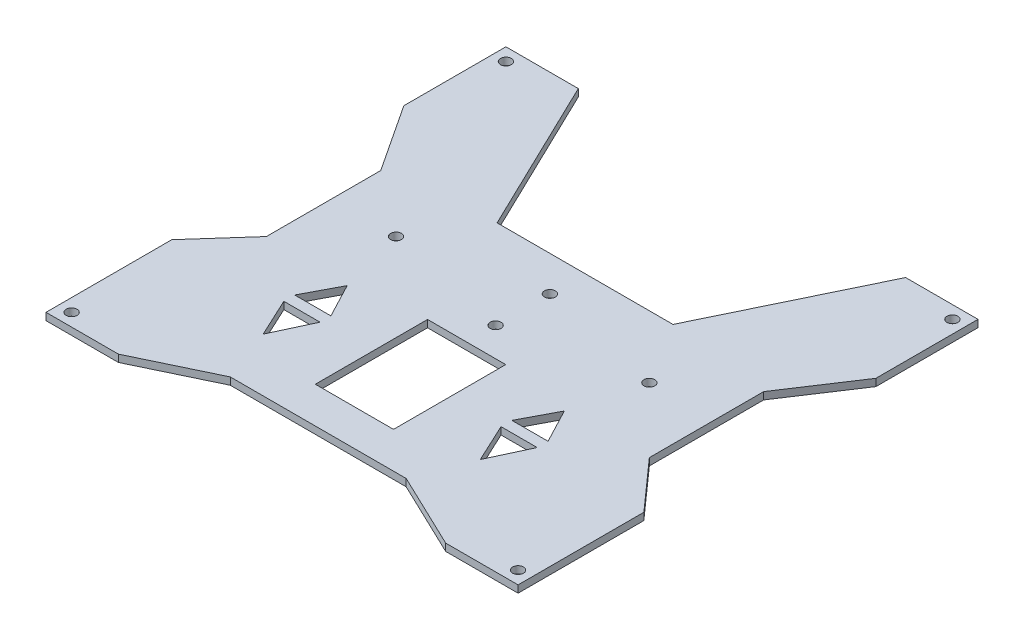
SolidWorks part; units mm, degrees
ref_plane "Front Plane" through (0, 0, 0) normal (0, 0, 1) x (1, 0, 0)
ref_plane "Top Plane" through (0, 0, 0) normal (0, 1, 0) x (1, 0, 0)
ref_plane "Right Plane" through (0, 0, 0) normal (1, 0, 0) x (0, 0, -1)
sketch "Sketch1" plane through (0, 0, 0) normal (0, 1, 0) x (1, 0, 0)
  line L0 (0, 0) -> (123.36, 0) construction
  line L1 (123.36, 0) -> (123.36, -120) construction
  line L2 (0, 0) -> (0, -120) construction
  line L3 (0, 0) -> (-3.5355, 3.5355) construction
  line L4 (123.36, -120) -> (126.8955, -123.5355) construction
  line L6 (-3.5355, 3.5355) -> (126.8955, 3.5355)
  line L7 (-3.5355, 3.5355) -> (-3.5355, -123.5355)
  line L8 (-3.5355, -123.5355) -> (126.8955, -123.5355)
  line L9 (126.8955, 3.5355) -> (126.8955, -123.5355)
  circle A0 centre (0, 0) radius 1.5
  circle A1 centre (123.36, 0) radius 1.5
  circle A2 centre (123.36, -120) radius 1.5
  circle A3 centre (0, -120) radius 1.5
  dimension "D1" = 123.36
  dimension "D2" = 120
  dimension "D3" = 5
  dimension "D4" = 5
extrude "Boss-Extrude1" add sketch "Sketch1" along normal blind 2 contours L9 L6 L7 L8 A3 A2 A1 A0 | L7 L6 L9 L8 | A3 | A0 | A1 | A2 region at (61.68, 0, 60)
sketch "Sketch3" plane through (0, 2, 0) normal (0, 1, 0) x (1, 0, 0)
  line L0 (-3.5355, -60) -> (126.8955, -60) construction
  line L5 (-3.5355, 3.5355) -> (-3.5355, -123.5355) construction
  line L6 (126.8955, 3.5355) -> (126.8955, -123.5355) construction
  line L7 (-3.5355, 3.5355) -> (16.4645, 3.5355) construction
  line L8 (-3.5355, 3.5355) -> (126.8955, 3.5355) construction
  line L10 (61.68, -60) -> (61.68, -45.9381) construction
  line L13 (16.4645, 3.5355) -> (106.8955, 3.5355)
  line L14 (-3.5355, -39.8122) -> (126.8955, -39.8122) construction
  line L15 (16.4645, 3.5355) -> (37.3799, -39.8122)
  line L16 (61.68, -45.9381) -> (61.68, -28.036) construction
  line L17 (37.3799, -39.8122) -> (85.9801, -39.8122)
  line L18 (106.8955, 3.5355) -> (85.9801, -39.8122)
  point P20 (61.68, -39.8122)
  dimension "D1" = 20
extrude "Cut-Extrude2" cut sketch "Sketch3" against normal blind 2
sketch "Sketch4" plane through (0, 2, 0) normal (0, 1, 0) x (1, 0, 0)
  line L0 (61.68, -123.5355) -> (61.68, -113.5355) construction
  line L1 (-3.5355, -123.5355) -> (126.8955, -123.5355) construction
  line L2 (-3.5355, -123.5355) -> (16.4645, -123.5355) construction
  line L3 (37.3799, -39.8122) -> (37.3799, -113.5355) construction
  line L4 (85.9801, -113.5355) -> (37.3799, -113.5355)
  line L5 (37.3799, -113.5355) -> (16.4645, -123.5355)
  line L6 (85.9801, -113.5355) -> (106.8955, -123.5355)
  line L7 (16.4645, -123.5355) -> (106.8955, -123.5355)
  dimension "D1" = 10
  dimension "D2" = 20
extrude "Cut-Extrude3" cut sketch "Sketch4" against normal blind 2
sketch "Sketch5" plane through (0, 2, 0) normal (0, 1, 0) x (1, 0, 0)
  line L0 (61.68, -113.5355) -> (61.68, -103.5355) construction
  line L1 (85.9801, -113.5355) -> (37.3799, -113.5355) construction
  line L2 (61.68, -103.5355) -> (61.68, -72.5355) construction
  line L3 (72.48, -88.0355) -> (50.88, -88.0355) construction
  line L4 (50.88, -88.0355) -> (50.88, -72.5355) construction
  line L5 (72.48, -88.0355) -> (72.48, -103.5355) construction
  line L7 (50.88, -72.5355) -> (72.48, -72.5355)
  line L8 (50.88, -72.5355) -> (50.88, -103.5355)
  line L9 (50.88, -103.5355) -> (72.48, -103.5355)
  line L10 (72.48, -72.5355) -> (72.48, -103.5355)
  point P8 (61.68, -88.0355)
  dimension "D1" = 10
  dimension "D2" = 31
  dimension "D3" = 10.8
extrude "Cut-Extrude4" cut sketch "Sketch5" against normal blind 10
sketch "Sketch6" plane through (0, 2, 0) normal (0, 1, 0) x (1, 0, 0)
  line L0 (61.68, -72.5355) -> (61.68, -64.5355) construction
  line L1 (72.48, -72.5355) -> (50.88, -72.5355) construction
  line L2 (61.68, -64.5355) -> (61.68, -49.5355) construction
  line L3 (61.68, -57.0355) -> (26.68, -57.0355) construction
  circle A0 centre (61.68, -64.5355) radius 1.5
  circle A1 centre (61.68, -49.5355) radius 1.5
  circle A2 centre (26.68, -57.0355) radius 1.5
  circle A3 centre (96.68, -57.0355) radius 1.5
  dimension "D2" = 15
  dimension "D3" = 35
  dimension "D1" = 8
extrude "Cut-Extrude5" cut sketch "Sketch6" against normal blind 10
sketch "Sketch7" plane through (0, 2, 0) normal (0, 1, 0) x (1, 0, 0)
  line L0 (61.68, -103.5355) -> (61.68, -72.5355) construction
  line L1 (50.88, -103.5355) -> (72.48, -103.5355) construction
  line L2 (72.48, -72.5355) -> (50.88, -72.5355) construction
  line L3 (61.68, -72.5355) -> (61.68, -88.0355) construction
  line L4 (61.68, -88.0355) -> (31.68, -88.0355) construction
  line L5 (31.68, -88.0355) -> (31.68, -85.0355) construction
  line L6 (36.68, -85.0355) -> (26.68, -85.0355)
  line L7 (26.68, -85.0355) -> (31.68, -75.5375)
  line L8 (36.68, -85.0355) -> (31.68, -75.5375)
  line L9 (31.68, -88.0355) -> (26.68, -88.0355)
  line L10 (26.68, -88.0355) -> (31.68, -98.7582)
  line L11 (31.68, -98.7582) -> (36.68, -88.0355)
  line L12 (36.68, -88.0355) -> (31.68, -88.0355)
  line L13 (86.68, -85.0355) -> (91.68, -75.5375)
  line L14 (96.68, -85.0355) -> (91.68, -75.5375)
  line L15 (86.68, -85.0355) -> (96.68, -85.0355)
  line L16 (91.68, -98.7582) -> (86.68, -88.0355)
  line L17 (96.68, -88.0355) -> (91.68, -98.7582)
  line L18 (91.68, -88.0355) -> (96.68, -88.0355)
  line L19 (86.68, -88.0355) -> (91.68, -88.0355)
  dimension "D1" = 30
  dimension "D2" = 3
  dimension "D3" = 5
extrude "Cut-Extrude6" cut sketch "Sketch7" against normal blind 10 contours L11 L12 L9 L10 | L6 L8 L7 | L19 L16 L17 L18 | L13 L15 L14 | L6 L7 L8 region at (31.68, 2, 81.8695) region at (31.68, 2, 91.6097) region at (91.68, 2, 81.8695) region at (91.68, 2, 91.6097)
sketch "Sketch8" plane through (0, 2, 0) normal (0, 1, 0) x (1, 0, 0)
  line L0 (-3.5355, 3.5355) -> (-3.5355, -123.5355) construction
  line L1 (-3.5355, -60) -> (8.7805, -60) construction
  line L2 (8.7805, -60) -> (8.7805, -43.3637)
  line L3 (8.7805, -43.3637) -> (-3.5355, -24.6713)
  line L4 (8.7805, -60) -> (8.7805, -74.9539)
  line L5 (8.7805, -74.9539) -> (-3.5355, -88.7863)
  line L6 (-3.5355, -24.6713) -> (-3.5355, -88.7863)
  line L7 (61.68, -113.5355) -> (61.68, -108.6003) construction
  line L8 (85.9801, -113.5355) -> (37.3799, -113.5355) construction
  line L9 (114.5795, -43.3637) -> (126.8955, -24.6713)
  line L10 (114.5795, -60) -> (114.5795, -43.3637)
  line L11 (114.5795, -60) -> (114.5795, -74.9539)
  line L12 (114.5795, -74.9539) -> (126.8955, -88.7863)
  line L13 (126.8955, -24.6713) -> (126.8955, -88.7863)
extrude "Cut-Extrude7" cut sketch "Sketch8" against normal blind 10 contours L6 L5 L4 L2 L3 | L9 L13 L12 L11 L10
